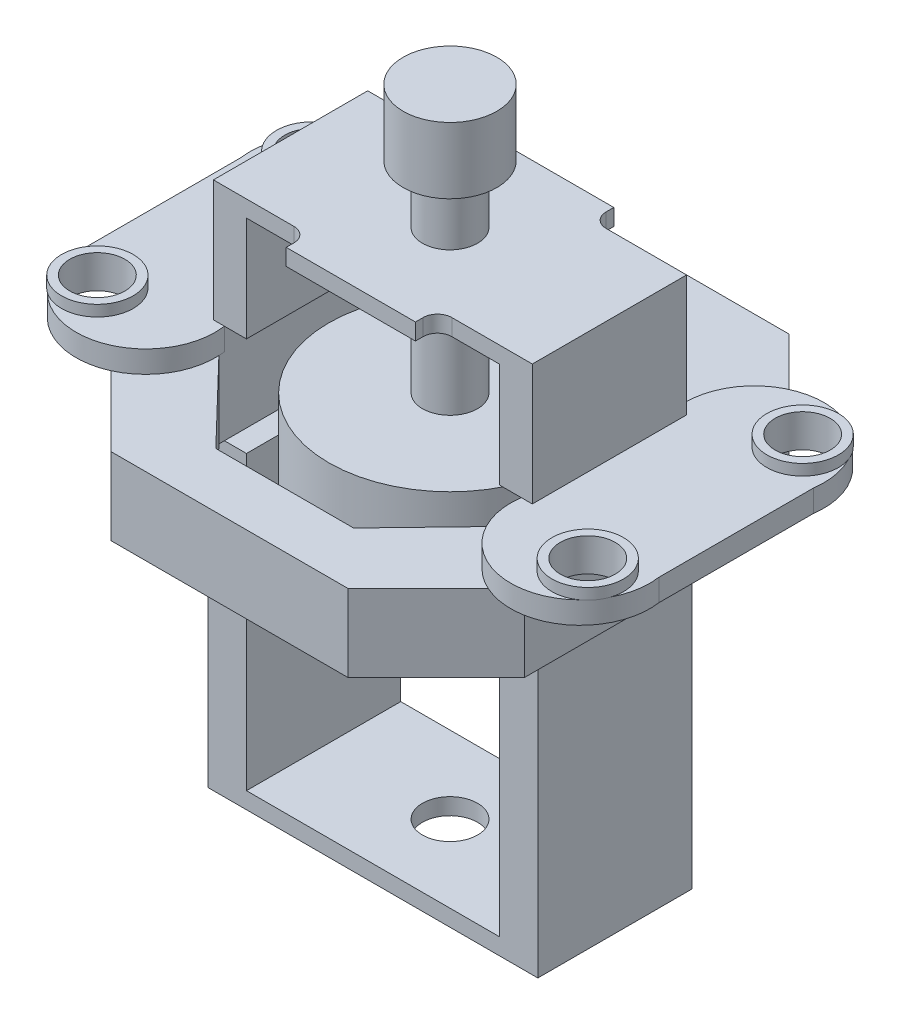
SolidWorks part; units mm, degrees
ref_plane "Alzado" through (0, 0, 0) normal (0, 0, 1) x (1, 0, 0)
ref_plane "Planta" through (0, 0, 0) normal (0, 1, 0) x (1, 0, 0)
ref_plane "Vista lateral" through (0, 0, 0) normal (1, 0, 0) x (0, 0, -1)
sketch "Croquis2" plane through (0, 0, 0) normal (0, 1, 0) x (1, 0, 0)
  line L0 (0, 0) -> (43, 0)
  line L3 (48.44, -55) -> (48.44, -25)
  line L4 (9, -10) -> (34, -10)
  line L5 (21.5, -80) -> (0, -80)
  line L6 (0, -80) -> (43, -80)
  line L7 (59, -64) -> (59, -16)
  line L8 (59, -16) -> (43, 0)
  line L9 (-16, -16) -> (0, 0)
  line L10 (-16, -64) -> (-16, -16)
  line L11 (-16, -64) -> (0, -80)
  line L12 (59, -64) -> (43, -80)
  line L13 (0, -80) -> (43, -80)
  line L14 (34, -10) -> (48.44, -25)
  line L15 (9, -70) -> (34, -70)
  line L16 (34, -70) -> (48.44, -55)
  line L17 (9, -70) -> (-5.44, -55)
  line L18 (9, -10) -> (-5.44, -25)
  line L19 (-5.44, -25) -> (-5.44, -55)
  point P20 (21.5, -70)
extrude "Saliente-Extruir1" add sketch "Croquis2" along normal blind 14 contours L12 L7 L8 L0 L9 L10 L11 L5 L6 L19 L18 L4 L14 L3 L16 L15 L17 region at (21.5, 0, 1.0966)
sketch "Croquis4" plane through (0, 14, 0) normal (0, 1, 0) x (1, 0, 0)
  circle A0 centre (21.5, -40) radius 22
  dimension "D1" = 44
extrude "Saliente-Extruir2" add sketch "Croquis4" against normal blind 15 separate body
sketch "Croquis5" plane through (0, 14, 0) normal (0, 1, 0) x (1, 0, 0)
  line L0 (-30.44, -26) -> (-30.44, -54)
  line L2 (48.44, -26) -> (48.44, -54)
  line L3 (73.44, -26) -> (73.44, -54)
  line L5 (-5.44, -26) -> (-5.44, -54)
  arc A0 (48.44, -26) -> (73.44, -26) centre (60.94, -24.2105) cw
  circle A1 centre (66, -20.5) radius 5
  circle A2 centre (66, -59.5) radius 5
  arc A3 (48.44, -54) -> (73.44, -54) centre (60.94, -55.7895) ccw
  arc A4 (-5.44, -54) -> (-30.44, -54) centre (-17.94, -55.7895) cw
  circle A5 centre (-23, -59.5) radius 5
  circle A6 centre (-23, -20.5) radius 5
  arc A7 (-5.44, -26) -> (-30.44, -26) centre (-17.94, -24.2105) ccw
  dimension "D1" = 10
extrude "Saliente-Extruir3" add sketch "Croquis5" along normal blind 4
sketch "Croquis7" plane through (0, 18, 0) normal (0, 1, 0) x (1, 0, 0)
  circle A0 centre (-23, -20.5) radius 5
  circle A1 centre (-23, -20.5) radius 6.5
  circle A2 centre (-23, -59.5) radius 5
  circle A3 centre (-23, -59.5) radius 6.5
  circle A4 centre (66, -59.5) radius 6.5
  circle A5 centre (66, -59.5) radius 5
  circle A6 centre (66, -20.5) radius 6.5
  circle A7 centre (66, -20.5) radius 5
  dimension "D1" = 13
extrude "Saliente-Extruir4" add sketch "Croquis7" along normal blind 2
sketch "Croquis8" plane through (0, 18, 0) normal (0, 1, 0) x (1, 0, 0)
  line L1 (-5.44, -26) -> (-1.44, -26)
  line L2 (-5.44, -54) -> (-1.44, -54)
  line L3 (-1.44, -54) -> (-1.44, -26)
  line L4 (-5.44, -26) -> (-7.44, -26)
  line L5 (-7.44, -26) -> (-7.44, -54)
  line L6 (-7.44, -54) -> (-5.44, -54)
  line L7 (50.44, -54) -> (48.44, -54)
  line L8 (50.44, -26) -> (50.44, -54)
  line L9 (48.44, -26) -> (50.44, -26)
  line L10 (44.44, -54) -> (44.44, -26)
  line L11 (48.44, -54) -> (44.44, -54)
  line L12 (48.44, -26) -> (44.44, -26)
extrude "Saliente-Extruir5" add sketch "Croquis8" along normal blind 19
sketch "Croquis9" plane through (0, 37, 0) normal (0, 1, 0) x (1, 0, 0)
  line L0 (-7.44, -26) -> (7.1735, -26)
  line L1 (50.44, -26) -> (50.44, -54)
  line L2 (50.44, -54) -> (35.8265, -54)
  line L3 (-7.44, -54) -> (-7.44, -26)
  line L4 (35.8265, -26) -> (50.44, -26)
  line L5 (9.7721, -23.4014) -> (9.7721, -22.001)
  line L6 (9.7721, -22.001) -> (33.2279, -22.001)
  line L7 (33.2279, -23.4014) -> (33.2279, -22.001)
  line L8 (7.1735, -54) -> (-7.44, -54)
  line L9 (33.2279, -56.5986) -> (33.2279, -57.999)
  line L10 (9.7721, -57.999) -> (33.2279, -57.999)
  line L11 (9.7721, -56.5986) -> (9.7721, -57.999)
  circle A0 centre (21.5, -40) radius 5
  arc A1 (7.1735, -54) -> (9.7721, -56.5986) centre (7.1735, -56.5986) cw
  arc A2 (33.2279, -56.5986) -> (35.8265, -54) centre (35.8265, -56.5986) cw
  arc A3 (35.8265, -26) -> (33.2279, -23.4014) centre (35.8265, -23.4014) cw
  arc A4 (9.7721, -23.4014) -> (7.1735, -26) centre (7.1735, -23.4014) cw
  point P16 (21.5, -22.001)
  point P22 (21.5, -57.999)
  dimension "D1" = 10
  dimension "D2" = 2.5986
extrude "Saliente-Extruir6" add sketch "Croquis9" along normal blind 3
sketch "Croquis10" plane through (0, 14, 0) normal (0, 1, 0) x (1, 0, 0)
  circle A0 centre (21.5, -40) radius 5
extrude "Saliente-Extruir7" add sketch "Croquis10" along normal blind 36.5
sketch "Croquis12" plane through (0, 50.5, 0) normal (0, 1, 0) x (1, 0, 0)
  circle A0 centre (21.5, -40) radius 8.5
  dimension "D1" = 17
extrude "Saliente-Extruir8" add sketch "Croquis12" along normal blind 12
sketch "Croquis13" plane through (0, 0, 0) normal (0, -1, 0) x (1, 0, 0)
  line L0 (-5.44, 54) -> (-1.44, 54)
  line L2 (-1.44, 54) -> (-1.44, 26)
  line L3 (48.44, 54) -> (51.44, 54)
  line L4 (51.44, 54) -> (51.44, 26)
  line L5 (-1.44, 26) -> (-5.44, 26)
  line L6 (-5.44, 26) -> (-8.44, 26)
  line L7 (-8.44, 26) -> (-8.44, 54)
  line L8 (-8.44, 54) -> (-5.44, 54)
  line L9 (48.44, 54) -> (44.44, 54)
  line L10 (44.44, 54) -> (44.44, 26)
  line L11 (44.44, 26) -> (51.44, 26)
  dimension "D1" = 3
  dimension "D2" = 3
extrude "Saliente-Extruir9" add sketch "Croquis13" along normal blind 53
sketch "Croquis14" plane through (0, -53, 0) normal (0, -1, 0) x (1, 0, 0)
  line L0 (-8.44, 54) -> (51.44, 54)
  line L1 (51.44, 54) -> (51.44, 26)
  line L2 (51.44, 26) -> (-8.44, 26)
  line L3 (-8.44, 26) -> (-8.44, 54)
  circle A0 centre (21.5, 40) radius 5
  dimension "D1" = 10
extrude "Saliente-Extruir10" add sketch "Croquis14" along normal blind 3
